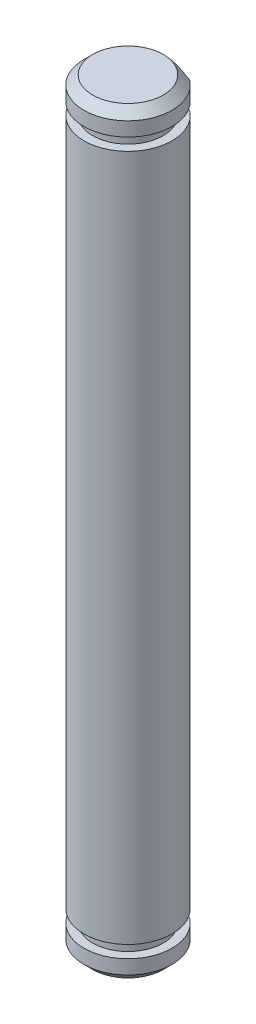
SolidWorks part; units mm, degrees
ref_plane "Front Plane" through (0, 0, 0) normal (0, 0, 1) x (1, 0, 0)
ref_plane "Top Plane" through (0, 0, 0) normal (0, 1, 0) x (1, 0, 0)
ref_plane "Right Plane" through (0, 0, 0) normal (1, 0, 0) x (0, 0, -1)
sketch "Sketch1" plane through (0, 0, 0) normal (0, 1, 0) x (1, 0, 0)
  circle A0 centre (-51.989, -23.1454) radius 2.5
extrude "Boss-Extrude1" add sketch "Sketch1" along normal blind 43
ref_axis "Axis1" through (-51.989, 43, 23.1454) along (0, -1, 0)
ref_plane "Plane2" through (0, 0, 23.1454) normal (0, 0, 1) x (1, 0, 0)
sketch "Sketch2" plane through (0, 43, 0) normal (0, 1, 0) x (1, 0, 0)
  line L0 (-50.4843, -21.1454) -> (-53.4937, -21.1454)
  arc A0 (-50.4843, -21.1454) -> (-53.4937, -21.1454) centre (-51.989, -23.1454) ccw
  dimension "D1" = 2
extrude "Cut-Extrude1" cut sketch "Sketch2" along a picked direction on the side against the normal through all
chamfer "Chamfer1" distance 0.5 angle 45 2 edges at (-51.989, 43, 25.6454) (-51.989, 0, 25.6454)
sketch "Sketch4" plane through (0, 0, 23.1454) normal (0, 0, 1) x (1, 0, 0)
  line L0 (-54.7765, 41.7) -> (-53.989, 41.7)
  line L1 (-53.989, 41.7) -> (-53.989, 41)
  line L2 (-53.989, 41) -> (-54.7765, 41)
  line L3 (-54.7765, 41) -> (-54.7765, 41.7)
  line L4 (-54.7765, 1.3) -> (-53.989, 1.3)
  line L5 (-53.989, 1.3) -> (-53.989, 2)
  line L6 (-53.989, 2) -> (-54.7765, 2)
  line L7 (-54.7765, 2) -> (-54.7765, 1.3)
  line L8 (-53.989, 0) -> (-49.989, 0) construction
  line L9 (-54.489, 42.5) -> (-54.489, 0.5) construction
  line L10 (-49.989, 43) -> (-53.989, 43) construction
  dimension "D1" = 1.3
  dimension "D2" = 0.7
  dimension "D3" = 0.5
  dimension "D4" = 1.3
  dimension "D5" = 0.7
  dimension "D6" = 0.5
revolve "Cut-Revolve6" cut sketch "Sketch4" angle 360 about axis through (-51.989, 43, 23.1454) along (0, -1, 0)
